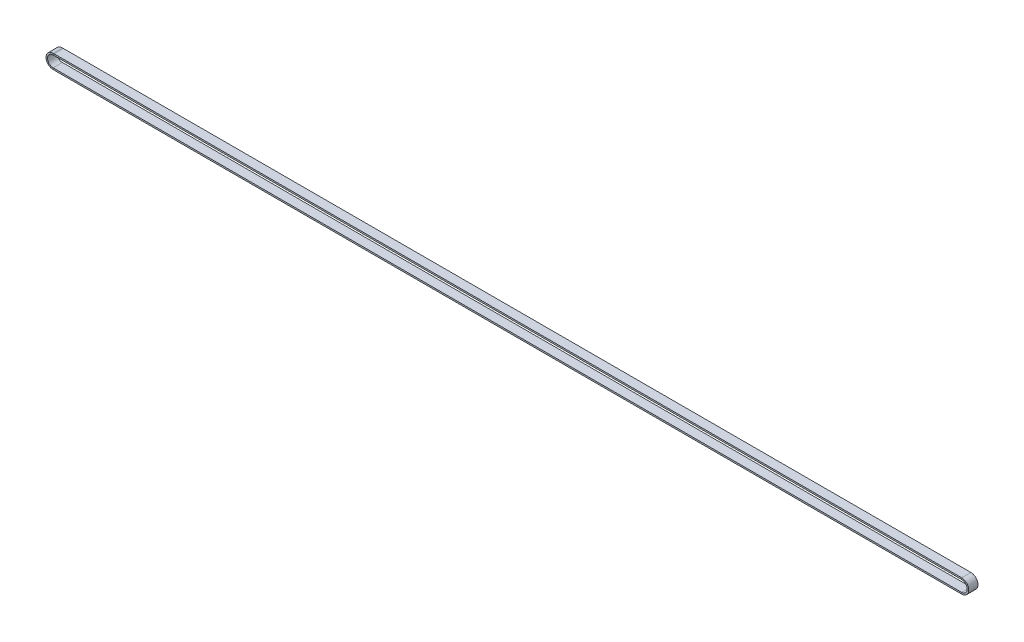
SolidWorks part; units mm, degrees
ref_plane "Front Plane" through (0, 0, 0) normal (0, 0, 1) x (1, 0, 0)
ref_plane "Top Plane" through (0, 0, 0) normal (0, 1, 0) x (1, 0, 0)
ref_plane "Right Plane" through (0, 0, 0) normal (1, 0, 0) x (0, 0, -1)
sketch "Sketch2" plane through (0, 0, 0) normal (0, 0, 1) x (1, 0, 0)
  line L0 (0, 0) -> (1, 0) construction
  line L1 (0, 0) -> (0, 1) construction
  line L2 (-1, -54.6414) -> (883.5206, -54.6414)
  line L3 (883.5206, -68.4414) -> (-1, -68.4414)
  arc A0 (-1, -68.4414) -> (-1, -54.6414) centre (-1, -61.5414) cw
  arc A1 (883.5206, -54.6414) -> (883.5206, -68.4414) centre (883.5206, -61.5414) cw
sketch "Sketch3" plane through (0, 0, 0) normal (1, 0, 0) x (0, 0, -1)
  line L1 (0, -56.1414) -> (-9, -56.1414)
  line L2 (0, -56.1414) -> (0, -54.6414)
  line L3 (0, -54.6414) -> (-9, -54.6414)
  line L4 (-9, -56.1414) -> (-9, -54.6414)
  dimension "D1" = 9
  dimension "D2" = 1.5
sweep "Sweep1" add profiles "Sketch3" path "Sketch2"
